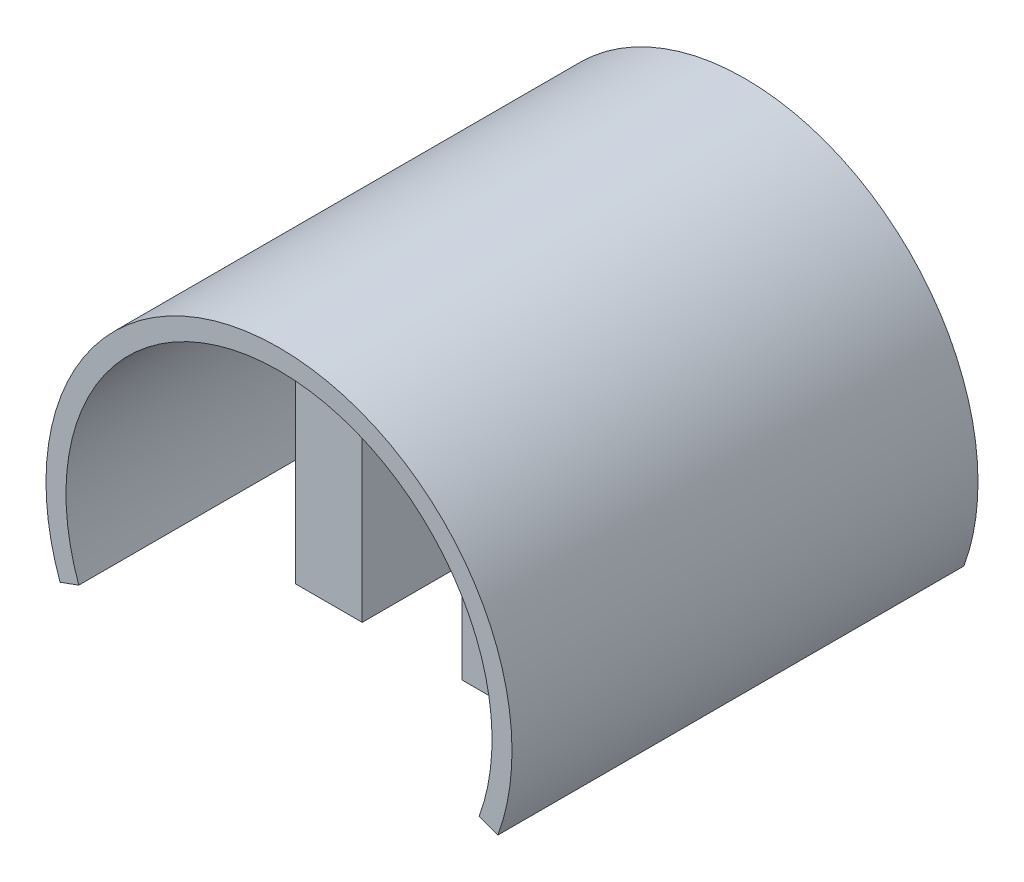
SolidWorks part; units mm, degrees
material "ABS"
ref_plane "Front" through (0, 0, 0) normal (0, 0, 1) x (1, 0, 0)
ref_plane "Top" through (0, 0, 0) normal (0, 1, 0) x (1, 0, 0)
ref_plane "Right" through (0, 0, 0) normal (1, 0, 0) x (0, 0, -1)
sketch "Esquisse1" plane through (0, 0, 0) normal (0, 0, 1) x (1, 0, 0)
  circle A0 centre (0, 0) radius 35
  circle A1 centre (0, 0) radius 32
  dimension "D1" = 70
  dimension "D2" = 3
extrude "Boss.-Extru.1" add sketch "Esquisse1" along normal blind 70
sketch "Esquisse2" plane through (0, 0, 70) normal (0, 0, 1) x (1, 0, 0)
  line L0 (0, 0) -> (0, 35) construction
  line L1 (-7.5, 31.1087) -> (-7.5, -31.1087)
  line L2 (-7.5, 0) -> (-17.5, 0) construction
  line L3 (-17.5, -26.7909) -> (-17.5, 26.7909)
  line L4 (7.5, 0) -> (17.5, 0) construction
  line L5 (17.5, -26.7909) -> (17.5, 26.7909)
  line L6 (7.5, 31.1087) -> (7.5, -31.1087)
  line L7 (0, 0) -> (0, -35) construction
  circle A0 centre (0, 0) radius 35 construction
  circle A1 centre (0, 0) radius 32 construction
  arc A2 (-17.5, 26.7909) -> (-7.5, 31.1087) centre (0, 0) cw
  arc A3 (17.5, 26.7909) -> (7.5, 31.1087) centre (0, 0) ccw
  arc A4 (17.5, -26.7909) -> (7.5, -31.1087) centre (0, 0) cw
  arc A5 (-17.5, -26.7909) -> (-7.5, -31.1087) centre (0, 0) ccw
  dimension "D1" = 10
  dimension "D2" = 35
extrude "Boss.-Extru.2" add sketch "Esquisse2" against normal blind 70
sketch "Esquisse3" plane through (0, 0, 0) normal (0, 1, 0) x (1, 0, 0)
  line L0 (-12.5, 0) -> (-12.5, -70) construction
  line L1 (35, 0) -> (-35, 0) construction
  line L2 (-35, -70) -> (35, -70) construction
  line L3 (-17.5, -25) -> (-7.5, -25) construction
  line L6 (0, -70) -> (0, 0) construction
  line L7 (17.5, -25) -> (7.5, -25) construction
  line L8 (-17.5, 0) -> (-17.5, -70) construction
  line L9 (-7.5, 0) -> (-7.5, -70) construction
  circle A0 centre (-12.5, -10) radius 3.5
  circle A1 centre (-12.5, -40) radius 3.5
  circle A2 centre (12.5, -40) radius 3.5
  circle A3 centre (12.5, -10) radius 3.5
  point P12 (-12.5, -25)
  point P26 (12.5, -25)
  point P40 (-12.5, -25)
  dimension "D1" = 7
  dimension "D3" = 10
  dimension "D2" = 15
extrude "Enlèv. mat.-Extru.1" cut sketch "Esquisse3" against normal blind 20 and the other way blind 20
sketch "Esquisse4" [suppressed] plane through (0, 0, 70) normal (0, 0, 1) x (1, 0, 0)
  line L0 (0, -10) -> (0, 0) construction
  line L1 (-50, 50) -> (50, 50)
  line L2 (-50, 50) -> (-50, -10)
  line L3 (-50, -10) -> (50, -10)
  line L4 (50, 50) -> (50, -10)
  dimension "D1" = 15
  dimension "D2" = 60
  dimension "D3" = 100
extrude "Enlèv. mat.-Extru.2" [suppressed] cut sketch "Esquisse4" against normal through all both and the other way through all
sketch "Esquisse5" plane through (0, 0, 70) normal (0, 0, 1) x (1, 0, 0)
  line L0 (0, -6.5) -> (0, 0) construction
  line L1 (-50, -56.5) -> (50, -56.5)
  line L2 (-50, -56.5) -> (-50, -6.5)
  line L3 (-50, -6.5) -> (50, -6.5)
  line L4 (50, -56.5) -> (50, -6.5)
  dimension "D1" = 6.5
  dimension "D2" = 50
  dimension "D3" = 100
extrude "Enlèv. mat.-Extru.3" cut sketch "Esquisse5" against normal through all
sketch "Esquisse7" plane through (0, -6.5, 0) normal (0, -1, 0) x (1, 0, 0)
  line L4 (-7.5, 0) -> (-7.5, 70)
  line L5 (-7.5, 70) -> (-17.5, 70)
  line L6 (-17.5, 70) -> (-17.5, 0)
  line L7 (-17.5, 0) -> (-7.5, 0)
  line L8 (-7.5, 0) -> (-7.5, 70)
  line L9 (-7.5, 70) -> (-17.5, 70)
  line L10 (-17.5, 70) -> (-17.5, 0)
  line L11 (-17.5, 0) -> (-7.5, 0)
  line L12 (17.5, 0) -> (17.5, 70)
  line L13 (17.5, 70) -> (7.5, 70)
  line L14 (7.5, 70) -> (7.5, 0)
  line L15 (7.5, 0) -> (17.5, 0)
  line L16 (17.5, 0) -> (17.5, 70)
  line L17 (17.5, 70) -> (7.5, 70)
  line L18 (7.5, 70) -> (7.5, 0)
  line L19 (7.5, 0) -> (17.5, 0)
  circle A0 centre (-12.5, 40) radius 3.5 construction
  circle A1 centre (-12.5, 40) radius 3.5
  circle A2 centre (-12.5, 10) radius 3.5 construction
  circle A3 centre (-12.5, 10) radius 3.5
  circle A4 centre (12.5, 40) radius 3.5 construction
  circle A5 centre (12.5, 40) radius 3.5
  circle A6 centre (12.5, 10) radius 3.5 construction
  circle A7 centre (12.5, 10) radius 3.5
  dimension "D1" = 0
  dimension "D2" = 0
extrude "Boss.-Extru.3" add sketch "Esquisse7" along normal blind 8
sketch "Esquisse8" plane through (0, 0, 70) normal (0, 0, 1) x (1, 0, 0)
  line L0 (32.8892, -11.9707) -> (30.0702, -10.9446)
  line L1 (30.0702, -10.9446) -> (0, 0) construction
  line L2 (34.3911, -6.5) -> (31.3329, -6.5) construction
  line L3 (0, 0) -> (0, 9.4102) construction
  line L4 (-32.8892, -11.9707) -> (-30.0702, -10.9446)
  line L5 (-34.3911, -6.5) -> (-31.3329, -6.5)
  line L6 (34.3911, -6.5) -> (31.3329, -6.5)
  arc A0 (31.3329, -6.5) -> (30.0702, -10.9446) centre (0, 0) cw
  arc A1 (34.3911, -6.5) -> (32.8892, -11.9707) centre (0, 0) cw
  arc A2 (-34.3911, -6.5) -> (-32.8892, -11.9707) centre (0, 0) ccw
  arc A3 (-31.3329, -6.5) -> (-30.0702, -10.9446) centre (0, 0) ccw
  dimension "D1" = 20
extrude "Boss.-Extru.5" add sketch "Esquisse8" against normal up to vertex (70 mm away) up to point (34.3911, -6.5, 0)
sketch "Esquisse10" plane through (0, 0, 70) normal (0, 0, 1) x (1, 0, 0)
  circle A0 centre (0, 0) radius 32
  dimension "D1" = 64
extrude "Enlèv. mat.-Extru.4" cut sketch "Esquisse10" against normal blind 20
fillet "Congé1" [suppressed] radius 2
fillet "Congé2" radius 2 4 edges at (-17.5, 26.7909, 25) (-7.5, 31.1087, 25) (17.5, 26.7909, 25) (7.5, 31.1087, 25)
